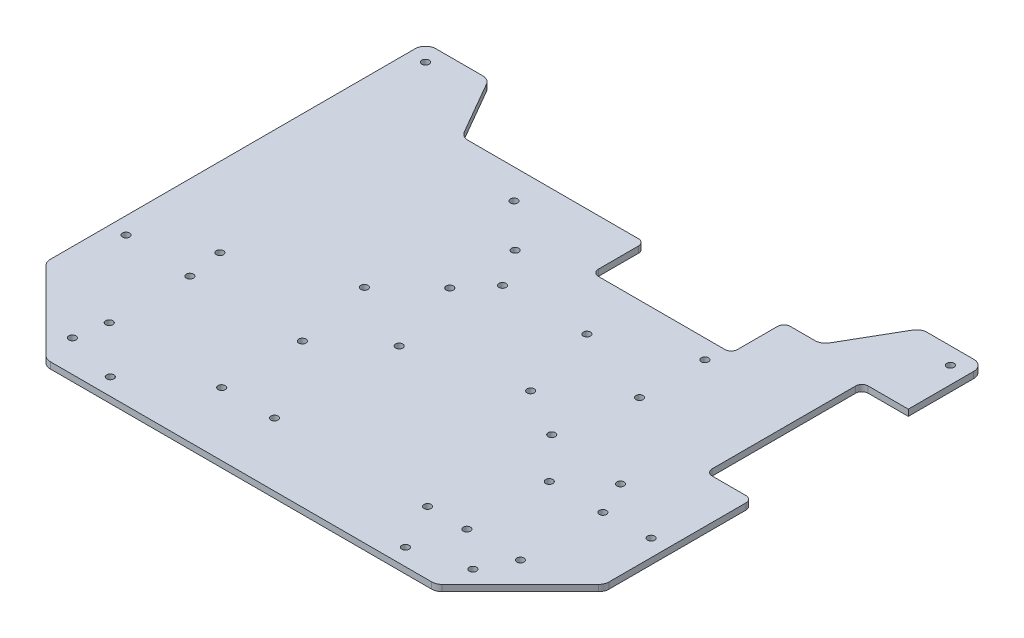
SolidWorks part; units mm, degrees
material "Acier non allié"
ref_plane "Front" through (0, 0, 0) normal (0, 0, 1) x (1, 0, 0)
ref_plane "Top" through (0, 0, 0) normal (0, 1, 0) x (1, 0, 0)
ref_plane "Right" through (0, 0, 0) normal (1, 0, 0) x (0, 0, -1)
sketch "Esquisse1" plane through (0, 0, 0) normal (0, 1, 0) x (1, 0, 0)
  line L0 (0, 0) -> (0, 190) construction
  line L1 (-92.5, 0) -> (92.5, 0)
  line L2 (92.5, 0) -> (132.5, 40)
  line L3 (132.5, 40) -> (132.5, 220)
  line L4 (132.5, 220) -> (102.5, 220)
  line L5 (102.5, 220) -> (85.1795, 190)
  line L6 (85.1795, 190) -> (-85.1795, 190)
  line L7 (-102.5, 220) -> (-85.1795, 190)
  line L8 (-132.5, 220) -> (-102.5, 220)
  line L9 (-132.5, 40) -> (-132.5, 220)
  line L10 (-92.5, 0) -> (-132.5, 40)
  dimension "D1" = 132.5
  dimension "D2" = 220
  dimension "D3" = 60
  dimension "D4" = 30
  dimension "D5" = 40
  dimension "D6" = 40
  dimension "D7" = 30
extrude "Boss.-Extru.1" add sketch "Esquisse1" along normal blind 3
fillet "Congé1" radius 5 10 edges at (92.5, 1.5, 0) (132.5, 1.5, -40) (132.5, 1.5, -220) (102.5, 1.5, -220) (85.1795, 1.5, -190) (-85.1795, 1.5, -190) (-102.5, 1.5, -220) (-132.5, 1.5, -220) (-92.5, 1.5, 0) (-132.5, 1.5, -40)
sketch "Esquisse2" plane through (0, 3, 0) normal (0, 1, 0) x (1, 0, 0)
  line L0 (0, 0) -> (0, 294.1173) construction
  line L2 (-90.4289, 0) -> (90.4289, 0) construction
  circle A0 centre (70, 8) radius 1
  circle A1 centre (124.5, 70) radius 1
  circle A2 centre (124.5, 212) radius 1
  circle A3 centre (-124.5, 212) radius 1
  circle A4 centre (-124.5, 70) radius 1
  circle A5 centre (-70, 8) radius 1
  dimension "D2" = 2
  dimension "D6" = 2
  dimension "D9" = 2
  dimension "D1" = 70
  dimension "D3" = 8
  dimension "D4" = 124.5
  dimension "D5" = 70
  dimension "D7" = 124.5
  dimension "D8" = 212
extrude "Enlèv. mat.-Extru.1" cut sketch "Esquisse2" against normal blind 3
hole_wizard "Dégagement M31" positions "Esquisse3" profile "Esquisse4" hole size "M3" standard "ISO" end condition through all
sketch "Esquisse3" plane through (0, 3, 0) normal (0, 1, 0) x (1, 0, 0)
  point P0 (70, 8)
  point P3 (-70, 8)
  point P6 (-124.5, 70)
  point P9 (-124.5, 212)
  point P12 (124.5, 212)
  point P15 (124.5, 70)
sketch "Esquisse4" plane through (70, 3, -8) normal (1, 0, 0) x (0, 0, 1)
  line L0 (0, 0) -> (0, 3)
  line L1 (0, 3) -> (1.7, 3)
  line L2 (1.7, 3) -> (1.7, 0)
  line L5 (1.7, 0) -> (0, 0)
  line L11 (0, -6.35) -> (0, 107.95) construction
  dimension "Diamètre du perçage jusqu'au prochain" = 3.4
  dimension "Profondeur du perçage jusqu'au prochain" = 3
sketch "Esquisse5" plane through (0, 3, 0) normal (0, 1, 0) x (1, 0, 0)
  line L0 (82.2927, 190) -> (-82.2927, 190) construction
  line L1 (67.5, 190) -> (1.5, 190)
  line L2 (67.5, 190) -> (67.5, 165)
  line L3 (67.5, 165) -> (1.5, 165)
  line L4 (1.5, 190) -> (1.5, 165)
  line L5 (132.5, 42.0711) -> (132.5, 215) construction
  line L6 (132.5, 184) -> (110.5, 184)
  line L7 (132.5, 184) -> (132.5, 110)
  line L8 (132.5, 110) -> (110.5, 110)
  line L9 (110.5, 184) -> (110.5, 110)
  line L10 (127.5, 220) -> (105.3868, 220) construction
  dimension "D1" = 25
  dimension "D2" = 65
  dimension "D3" = 131
  dimension "D4" = 36
  dimension "D5" = 110
  dimension "D6" = 22
extrude "Enlèv. mat.-Extru.2" cut sketch "Esquisse5" against normal through all
fillet "Congé2" radius 3 7 edges at (132.5, 1.5, -110) (110.5, 1.5, -110) (110.5, 1.5, -184) (67.5, 1.5, -190) (67.5, 1.5, -165) (1.5, 1.5, -165) (1.5, 1.5, -190)
sketch "Esquisse6" plane through (0, 3, 0) normal (0, 1, 0) x (1, 0, 0)
  line L0 (110.5, 140.5) -> (-167.6757, 140.5) construction
  line L1 (110.5, 181) -> (110.5, 113) construction
  line L2 (-90.4289, 0) -> (90.4289, 0) construction
  line L3 (110.5, 181) -> (110.5, 113) construction
  circle A0 centre (64, 156) radius 1
  circle A1 centre (-26, 156) radius 1
  circle A2 centre (-46.5, 176) radius 1
  circle A3 centre (64, 125) radius 1
  circle A4 centre (-26, 125) radius 1
  circle A5 centre (-46.5, 105) radius 1
  dimension "D4" = 2
  dimension "D6" = 2
  dimension "D10" = 2
  dimension "D1" = 140.5
  dimension "D2" = 46.5
  dimension "D3" = 15.5
  dimension "D5" = 136.5
  dimension "D7" = 15.5
  dimension "D8" = 35.5
  dimension "D9" = 157
extrude "Enlèv. mat.-Extru.3" cut sketch "Esquisse6" against normal through all
hole_wizard "Dégagement M32" positions "Esquisse7" profile "Esquisse8" hole size "M3" standard "ISO"
sketch "Esquisse7" plane through (0, 3, 0) normal (0, 1, 0) x (1, 0, 0)
  point P0 (-46.5, 105)
  point P3 (-26, 125)
  point P6 (-26, 156)
  point P9 (-46.5, 176)
  point P12 (64, 156)
  point P15 (64, 125)
sketch "Esquisse8" plane through (-46.5, 3, -105) normal (1, 0, 0) x (0, 0, 1)
  line L0 (0, 0) -> (0, 11.0215)
  line L1 (0, 11.0215) -> (1.7, 10)
  line L2 (1.7, 10) -> (1.7, 0)
  line L5 (1.7, 0) -> (0, 0)
  line L10 (0, 11.0215) -> (-1.7, 10) construction
  line L11 (0, -6.35) -> (0, 107.95) construction
  dimension "Diamètre du perçage" = 3.4
  dimension "Profondeur du perçage" = 10
  dimension "Angle de pointe" = 118
sketch "Esquisse9" plane through (0, 3, 0) normal (0, 1, 0) x (1, 0, 0)
  line L0 (132.5, 42.0711) -> (132.5, 107) construction
  line L1 (-90.4289, 0) -> (90.4289, 0) construction
  line L2 (-132.5, 215) -> (-132.5, 42.0711) construction
  line L3 (-39.16, 30) -> (-92.5, 30) construction
  line L4 (-39.16, 30) -> (-39.16, 68.24) construction
  line L5 (-39.16, 68.24) -> (-92.5, 68.24) construction
  line L6 (-92.5, 30) -> (-92.5, 68.24) construction
  line L7 (-14.16, 30) -> (-14.16, 89.182) construction
  line L8 (4.5, 165) -> (64.5, 165) construction
  line L9 (25.4456, 138.5886) -> (-14.5544, 138.5886) construction
  circle A0 centre (102.5, 30) radius 1
  circle A1 centre (77.1, 30) radius 1
  circle A2 centre (77.1, 69.12) radius 1
  circle A3 centre (102.5, 69.12) radius 1
  circle A6 centre (-92.5, 68.24) radius 1
  circle A7 centre (-39.16, 68.24) radius 1
  circle A8 centre (-39.16, 30) radius 1
  circle A9 centre (-92.5, 30) radius 1
  circle A10 centre (-14.16, 89.182) radius 1
  circle A11 centre (58.4456, 88.928) radius 1
  circle A12 centre (-14.16, 30) radius 1
  circle A13 centre (58.484, 30) radius 1
  circle A14 centre (-14.5544, 138.5886) radius 1
  circle A15 centre (25.4456, 138.5886) radius 1
  circle A16 centre (35.4456, 101.928) radius 1
  dimension "D1" = 2
  dimension "D2" = 2
  dimension "D3" = 2
  dimension "D4" = 2
  dimension "D17" = 2
  dimension "D18" = 2
  dimension "D19" = 2
  dimension "D20" = 2
  dimension "D21" = 2
  dimension "D22" = 2
  dimension "D23" = 2
  dimension "D24" = 2
  dimension "D32" = 2
  dimension "D33" = 2
  dimension "D34" = 2
  dimension "D5" = 30
  dimension "D6" = 30
  dimension "D7" = 25.4
  dimension "D8" = 25.4
  dimension "D9" = 39.12
  dimension "D10" = 39.12
  dimension "D11" = 30
  dimension "D12" = 30
  dimension "D13" = 38.24
  dimension "D14" = 53.34
  dimension "D15" = 30
  dimension "D16" = 40
  dimension "D25" = 72.606
  dimension "D26" = 72.644
  dimension "D27" = 59.182
  dimension "D28" = 58.928
  dimension "D29" = 25
  dimension "D30" = 30
  dimension "D31" = 30
  dimension "D35" = 13
  dimension "D36" = 38
  dimension "D37" = 40
  dimension "D38" = 23
  dimension "D39" = 10
extrude "Enlèv. mat.-Extru.4" cut sketch "Esquisse9" against normal through all
hole_wizard "Dégagement M33" positions "Esquisse10" profile "Esquisse11" hole size "M3" standard "ISO"
sketch "Esquisse10" plane through (0, 3, 0) normal (0, 1, 0) x (1, 0, 0)
  point P0 (77.1, 30)
  point P3 (102.5, 30)
  point P6 (77.1, 69.12)
  point P9 (102.5, 69.12)
sketch "Esquisse11" plane through (77.1, 3, -30) normal (1, 0, 0) x (0, 0, 1)
  line L0 (0, 0) -> (0, 11.0215)
  line L1 (0, 11.0215) -> (1.7, 10)
  line L2 (1.7, 10) -> (1.7, 0)
  line L5 (1.7, 0) -> (0, 0)
  line L10 (0, 11.0215) -> (-1.7, 10) construction
  line L11 (0, -6.35) -> (0, 107.95) construction
  dimension "Diamètre du perçage" = 3.4
  dimension "Profondeur du perçage" = 10
  dimension "Angle de pointe" = 118
sketch "Esquisse12" plane through (0, 3, 0) normal (0, 1, 0) x (1, 0, 0)
  line L2 (-90.4289, 0) -> (90.4289, 0) construction
  line L3 (95, 15) -> (-95, 15) construction
  line L4 (95, 15) -> (95, 85) construction
  line L5 (95, 85) -> (-95, 85) construction
  line L6 (-95, 15) -> (-95, 85) construction
  line L7 (132.5, 42.0711) -> (132.5, 107) construction
  circle A4 centre (-95, 85) radius 1
  circle A5 centre (95, 85) radius 1
  circle A6 centre (95, 15) radius 1
  circle A7 centre (-95, 15) radius 1
  point P6 (95, 50)
  dimension "D5" = 2
  dimension "D6" = 2
  dimension "D7" = 2
  dimension "D8" = 2
  dimension "D1" = 70
  dimension "D2" = 190
  dimension "D3" = 15
  dimension "D4" = 37.5
extrude "Enlèv. mat.-Extru.5" cut sketch "Esquisse12" against normal through all and the other way through all
hole_wizard "Dégagement M34" positions "Esquisse13" profile "Esquisse14" hole size "M3" standard "ISO"
sketch "Esquisse13" plane through (0, 3, 0) normal (0, 1, 0) x (1, 0, 0)
  point P3 (-92.5, 68.24)
  point P6 (-92.5, 30)
  point P9 (-39.16, 30)
  point P12 (-39.16, 68.24)
  point P16 (-14.16, 30)
  point P19 (58.484, 30)
  point P22 (-14.16, 89.182)
  point P25 (58.4456, 88.928)
  point P29 (35.4456, 101.928)
  point P32 (25.4456, 138.5886)
  point P35 (-14.5544, 138.5886)
sketch "Esquisse14" plane through (-92.5, 3, -68.24) normal (1, 0, 0) x (0, 0, 1)
  line L0 (0, 0) -> (0, 11.0215)
  line L1 (0, 11.0215) -> (1.7, 10)
  line L2 (1.7, 10) -> (1.7, 0)
  line L5 (1.7, 0) -> (0, 0)
  line L10 (0, 11.0215) -> (-1.7, 10) construction
  line L11 (0, -6.35) -> (0, 107.95) construction
  dimension "Diamètre du perçage" = 3.4
  dimension "Profondeur du perçage" = 10
  dimension "Angle de pointe" = 118
hole_wizard "Dégagement M35" positions "Esquisse15" profile "Esquisse16" hole size "M3" standard "ISO"
sketch "Esquisse15" plane through (0, 3, 0) normal (0, 1, 0) x (1, 0, 0)
  point P0 (-95, 15)
  point P3 (-95, 85)
  point P6 (95, 85)
  point P9 (95, 15)
sketch "Esquisse16" plane through (-95, 3, -15) normal (1, 0, 0) x (0, 0, 1)
  line L0 (0, 0) -> (0, 11.0215)
  line L1 (0, 11.0215) -> (1.7, 10)
  line L2 (1.7, 10) -> (1.7, 0)
  line L5 (1.7, 0) -> (0, 0)
  line L10 (0, 11.0215) -> (-1.7, 10) construction
  line L11 (0, -6.35) -> (0, 107.95) construction
  dimension "Diamètre du perçage" = 3.4
  dimension "Profondeur du perçage" = 10
  dimension "Angle de pointe" = 118
equation "\"WIDTH\"= 300mm'Total width of the robot"
equation "\"LENGTH\"= 220mm'Total length of the robot"
equation "\"CUT_DEPTH\"= 45mm'Depth of the cut on the edges of the plate"
equation "\"Plate_th\"= 3mm'Thickness of the plate"
equation "\"D1\"= \"Plate_th\""
